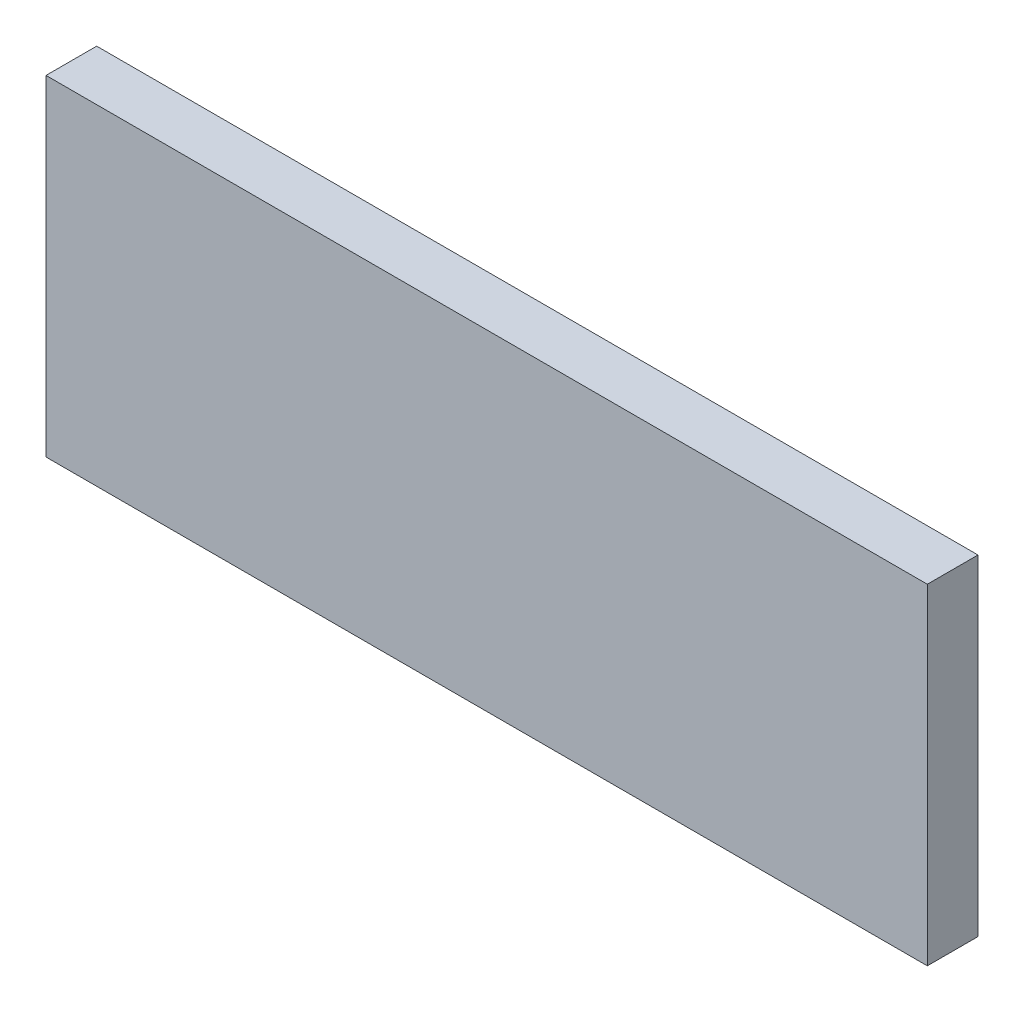
SolidWorks part; units mm, degrees
material "ABS PC"
ref_plane "Front Plane" through (0, 0, 0) normal (0, 0, 1) x (1, 0, 0)
ref_plane "Top Plane" through (0, 0, 0) normal (0, 1, 0) x (1, 0, 0)
ref_plane "Right Plane" through (0, 0, 0) normal (1, 0, 0) x (0, 0, -1)
sketch "Sketch1" plane through (0, 0, 0) normal (0, 0, 1) x (1, 0, 0)
  line L1 (0, 0) -> (50.8, 0)
  line L2 (0, 0) -> (0, 19.05)
  line L3 (0, 19.05) -> (50.8, 19.05)
  line L4 (50.8, 0) -> (50.8, 19.05)
  dimension "D1" = 19.05
  dimension "D2" = 50.8
extrude "Boss-Extrude1" add sketch "Sketch1" against normal blind 2.921
